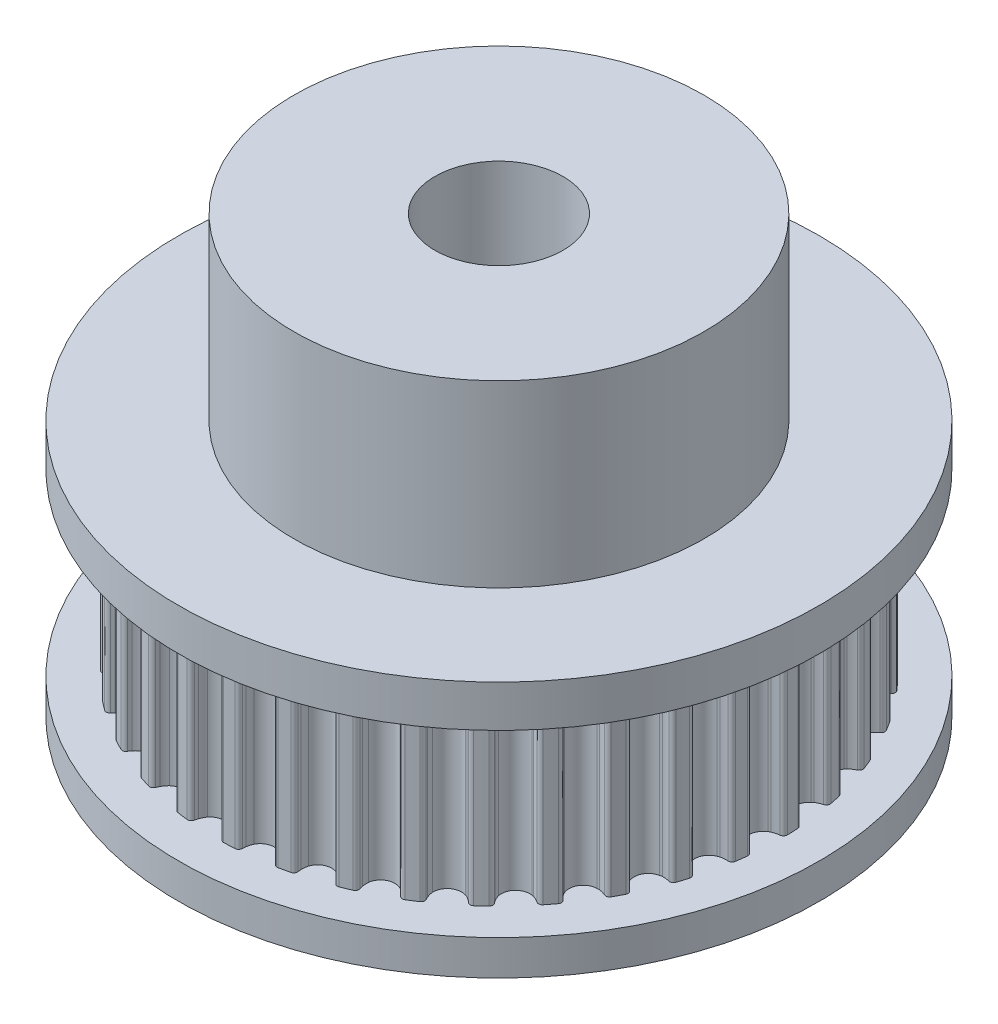
SolidWorks part; units mm, degrees
ref_plane "Płaszczyzna przednia" through (0, 0, 0) normal (0, 0, 1) x (1, 0, 0)
ref_plane "Płaszczyzna górna" through (0, 0, 0) normal (0, 1, 0) x (1, 0, 0)
ref_plane "Płaszczyzna prawa" through (0, 0, 0) normal (1, 0, 0) x (0, 0, -1)
sketch "Sketch1" plane through (0, 0, 0) normal (0, 0, 1) x (1, 0, 0)
  line L0 (0, 0) -> (0, 10.7402) construction
  line L1 (2.5, 0) -> (12.5, 0)
  line L2 (12.5, 0) -> (12.5, 1.3674)
  line L3 (12.5, 1.3674) -> (11, 1.3674)
  line L4 (11, 1.3674) -> (11, 8.3674)
  line L5 (11, 8.3674) -> (12.5, 8.3674)
  line L6 (12.5, 8.3674) -> (12.5, 10)
  line L7 (12.5, 10) -> (8, 10)
  line L8 (8, 10) -> (8, 17)
  line L9 (8, 17) -> (2.5, 17)
  line L10 (2.5, 17) -> (2.5, 0)
  dimension "D1" = 2.5
  dimension "D2" = 12.5
  dimension "D3" = 8.5
  dimension "D4" = 10
  dimension "D5" = 7
  dimension "D6" = 10
  dimension "D7" = 17
  dimension "D8" = 8
revolve "Revolve1" add sketch "Sketch1" angle 360 about L0
ref_plane "Plane2" through (0, 8.3674, 0) normal (0, -1, 0) x (-1, 0, 0)
sketch "Sketch3" plane through (0, 8.3674, 0) normal (0, -1, 0) x (-1, 0, 0)
  circle A0 centre (0, 0) radius 11
  circle A1 centre (0, 0) radius 2.5
  circle A2 centre (0, 0) radius 2.5
  circle A3 centre (0, 0) radius 11
sketch "Sketch5" plane through (0, 8.3674, 0) normal (0, -1, 0) x (-1, 0, 0)
  line L0 (0, 0) -> (7.4152, 7.4261) construction
  line L1 (0, 0) -> (8.0455, 6.7611) construction
  line L4 (0, 0) -> (9.006, 6.316) construction
  arc A1 (8.4213, 7.0769) -> (7.7724, 7.7839) centre (0, 0) ccw
  arc A2 (7.4152, 7.4261) -> (8.0455, 6.7611) centre (7.9577, 7.3091) ccw
  arc A3 (7.6868, 7.8685) -> (7.5189, 7.6635) centre (8.3696, 7.1379) ccw
  arc A4 (8.133, 6.7749) -> (8.498, 6.9846) centre (7.8286, 7.7275) ccw
  arc A6 (8.0455, 6.7611) -> (8.133, 6.7749) centre (8.0143, 7.2403) ccw
  arc A7 (8.498, 6.9846) -> (7.6868, 7.8685) centre (0, 0) ccw
  arc A8 (7.4152, 7.4261) -> (7.5189, 7.6635) centre (8.2998, 7.181) cw
  dimension "D2" = 22
  dimension "D4" = 2
  dimension "D5" = 5
  dimension "D6" = 2
  dimension "D8" = 22
  dimension "D3" = 5
  dimension "D9" = 11
extrude "Cut-Extrude1" cut sketch "Sketch5" along normal blind 7 contours A8 A2 A6 A4 A7 A1 A3 region at (-7.8642, 8.3674, -7.2186)
fillet "Fillet4" radius 0.15 2 edges at (-7.6868, 4.8674, -7.8685) (-8.498, 4.8674, -6.9846)
pattern_circular "CirPattern1" count 36 over 360 about axis through (0, 0, 0) along (0, -1, 0) of "Cut-Extrude1", "Fillet4" reverse direction yes
